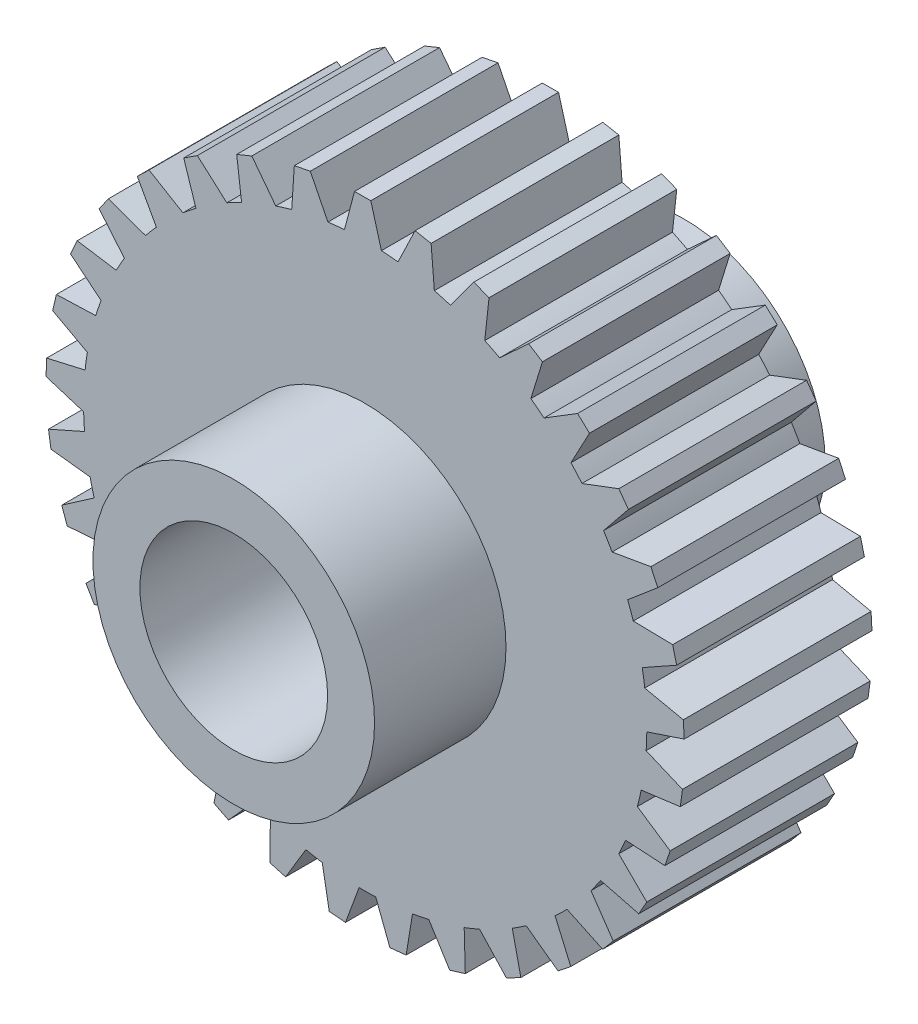
SolidWorks part; units mm, degrees
ref_plane "Front Plane" through (0, 0, 0) normal (0, 0, 1) x (1, 0, 0)
ref_plane "Top Plane" through (0, 0, 0) normal (0, 1, 0) x (1, 0, 0)
ref_plane "Right Plane" through (0, 0, 0) normal (1, 0, 0) x (0, 0, -1)
sketch "Sketch1" plane through (0, 0, 0) normal (0, 0, 1) x (1, 0, 0)
  line L0 (-1.1026, 14.9594) -> (-0.569, 16.9905)
  line L1 (-0.569, 16.9905) -> (0.2995, 16.9974)
  line L2 (0.2995, 16.9974) -> (0.8653, 14.975)
  line L3 (3.5108, 16.6335) -> (3.6837, 14.5406)
  line L4 (1.7484, 14.8978) -> (2.6568, 16.7911)
  line L5 (2.6568, 16.7911) -> (3.5108, 16.6335)
  line L6 (6.5953, 15.6685) -> (6.369, 13.5807)
  line L7 (4.5362, 14.2977) -> (5.7865, 15.9849)
  line L8 (5.7865, 15.9849) -> (6.5953, 15.6685)
  line L9 (9.4414, 14.1372) -> (8.824, 12.13)
  line L10 (7.1601, 13.1808) -> (8.7071, 14.6009)
  line L11 (8.7071, 14.6009) -> (9.4414, 14.1372)
  line L12 (11.9463, 12.0949) -> (10.9602, 10.2408)
  line L13 (9.5252, 11.5875) -> (11.313, 12.6892)
  line L14 (11.313, 12.6892) -> (11.9463, 12.0949)
  line L15 (14.0194, 9.6155) -> (12.7002, 7.9815)
  line L16 (11.546, 9.5755) -> (13.51, 10.3189)
  line L17 (13.51, 10.3189) -> (14.0194, 9.6155)
  line L18 (15.5857, 6.7886) -> (13.9812, 5.4338)
  line L19 (13.1495, 7.2174) -> (15.2187, 7.5757)
  line L20 (15.2187, 7.5757) -> (15.5857, 6.7886)
  line L21 (16.5888, 3.7163) -> (14.7569, 2.6896)
  line L22 (14.2778, 4.5984) -> (16.3774, 4.5586)
  line L23 (16.3774, 4.5586) -> (16.5888, 3.7163)
  line L24 (16.9924, 0.5096) -> (14.9992, -0.1518)
  line L25 (14.89, 1.8132) -> (16.9442, 1.3768)
  line L26 (16.9442, 1.3768) -> (16.9924, 0.5096)
  line L27 (16.7817, -2.7154) -> (14.6995, -2.9876)
  line L28 (14.9641, -1.0375) -> (16.8985, -1.8548)
  line L29 (16.8985, -1.8548) -> (16.7817, -2.7154)
  line L30 (15.9646, -5.8423) -> (13.8684, -5.7155)
  line L31 (14.4973, -3.8508) -> (16.2421, -5.0194)
  line L32 (16.2421, -5.0194) -> (15.9646, -5.8423)
  line L33 (14.5704, -8.758) -> (12.5361, -8.2369)
  line L34 (13.5066, -6.5248) -> (14.9987, -8.0025)
  line L35 (14.9987, -8.0025) -> (14.5704, -8.758)
  line L36 (12.6496, -11.3572) -> (10.7507, -10.4605)
  line L37 (12.0276, -8.963) -> (13.2131, -10.6964)
  line L38 (13.2131, -10.6964) -> (12.6496, -11.3572)
  line L39 (10.2717, -13.5459) -> (8.5768, -12.306)
  line L40 (10.114, -11.0773) -> (10.9501, -13.0037)
  line L41 (10.9501, -13.0037) -> (10.2717, -13.5459)
  line L42 (7.5225, -15.2451) -> (6.0929, -13.7068)
  line L43 (7.8349, -12.7912) -> (8.2912, -14.841)
  line L44 (8.2912, -14.841) -> (7.5225, -15.2451)
  line L45 (4.5014, -16.3932) -> (3.3887, -14.6122)
  line L46 (5.2725, -14.0428) -> (5.3327, -16.1419)
  line L47 (5.3327, -16.1419) -> (4.5014, -16.3932)
  line L48 (1.3176, -16.9489) -> (0.5621, -14.9895)
  line L49 (2.5196, -14.7869) -> (2.1814, -16.8595)
  line L50 (2.1814, -16.8595) -> (1.3176, -16.9489)
  line L51 (-1.9138, -16.8919) -> (-2.2848, -14.825)
  line L52 (-0.3243, -14.9965) -> (-1.0487, -16.9676)
  line L53 (-1.0487, -16.9676) -> (-1.9138, -16.8919)
  line L54 (-5.076, -16.2245) -> (-5.0492, -14.1247)
  line L55 (-3.1566, -14.6641) -> (-4.2408, -16.4625)
  line L56 (-4.2408, -16.4625) -> (-5.076, -16.2245)
  line L57 (-8.0548, -14.9706) -> (-7.631, -12.9138)
  line L58 (-5.8747, -13.8017) -> (-7.2798, -15.3625)
  line L59 (-7.2798, -15.3625) -> (-8.0548, -14.9706)
  line L60 (-10.7425, -13.1757) -> (-9.9371, -11.2363)
  line L61 (-8.3806, -12.4405) -> (-10.0556, -13.7071)
  line L62 (-10.0556, -13.7071) -> (-10.7425, -13.1757)
  line L63 (-13.0419, -10.9046) -> (-11.884, -9.1526)
  line L64 (-10.5835, -10.6297) -> (-12.468, -11.5564)
  line L65 (-12.468, -11.5564) -> (-13.0419, -10.9046)
  line L66 (-14.8699, -8.2393) -> (-13.4014, -6.7382)
  line L67 (-12.4039, -8.4346) -> (-14.4297, -8.988)
  line L68 (-14.4297, -8.988) -> (-14.8699, -8.2393)
  line L69 (-16.1605, -5.2763) -> (-14.4344, -4.0802)
  line L70 (-13.776, -5.9347) -> (-15.8699, -6.0947)
  line L71 (-15.8699, -6.0947) -> (-16.1605, -5.2763)
  line L72 (-16.867, -2.1226) -> (-14.9457, -1.2747)
  line L73 (-14.6502, -3.2204) -> (-16.7366, -2.9812)
  line L74 (-16.7366, -2.9812) -> (-16.867, -2.1226)
  line L75 (-16.9639, 1.1079) -> (-14.9169, 1.5768)
  line L76 (-14.9949, -0.3896) -> (-16.9983, 0.2401)
  line L77 (-16.9983, 0.2401) -> (-16.9639, 1.1079)
  line L78 (-16.4476, 4.2983) -> (-14.3489, 4.3714)
  line L79 (-14.7977, 2.4553) -> (-16.6457, 3.4527)
  line L80 (-16.6457, 3.4527) -> (-16.4476, 4.2983)
  line L81 (-15.3369, 7.3334) -> (-13.2623, 7.0079)
  line L82 (-14.0656, 5.2114) -> (-15.6914, 6.5405)
  line L83 (-15.6914, 6.5405) -> (-15.3369, 7.3334)
  line L84 (-13.6719, 10.1034) -> (-11.6964, 9.3912)
  line L85 (-12.8252, 7.7791) -> (-14.1701, 9.392)
  line L86 (-14.1701, 9.392) -> (-13.6719, 10.1034)
  line L87 (-11.5128, 12.5082) -> (-9.7077, 11.435)
  line L88 (-11.1212, 10.0657) -> (-12.1366, 11.904)
  line L89 (-12.1366, 11.904) -> (-11.5128, 12.5082)
  line L90 (-8.9375, 14.461) -> (-7.3682, 13.0656)
  line L91 (-9.0153, 11.9885) -> (-9.6644, 13.9857)
  line L92 (-9.6644, 13.9857) -> (-8.9375, 14.461)
  line L93 (-6.0393, 15.8911) -> (-4.7624, 14.2239)
  line L94 (-6.5835, 13.478) -> (-6.8429, 15.5619)
  line L95 (-6.8429, 15.5619) -> (-6.0393, 15.8911)
  line L96 (-2.9227, 16.7469) -> (-1.9844, 14.8682)
  line L97 (-3.9138, 14.4804) -> (-3.7742, 16.5758)
  line L98 (-3.7742, 16.5758) -> (-2.9227, 16.7469)
  arc A0 (1.7484, 14.8978) -> (0.8653, 14.975) centre (0, 0) ccw
  arc A1 (0.2995, 16.9974) -> (-0.569, 16.9905) centre (0, 0) ccw
  arc A2 (4.5362, 14.2977) -> (3.6837, 14.5406) centre (0, 0) ccw
  circle A3 centre (0, 0) radius 17 construction
  circle A4 centre (0, 0) radius 15 construction
  arc A5 (7.1601, 13.1808) -> (6.369, 13.5807) centre (0, 0) ccw
  arc A6 (9.5252, 11.5875) -> (8.824, 12.13) centre (0, 0) ccw
  arc A7 (11.546, 9.5755) -> (10.9602, 10.2408) centre (0, 0) ccw
  arc A8 (13.1495, 7.2174) -> (12.7002, 7.9815) centre (0, 0) ccw
  arc A9 (14.2778, 4.5984) -> (13.9812, 5.4338) centre (0, 0) ccw
  arc A10 (14.89, 1.8132) -> (14.7569, 2.6896) centre (0, 0) ccw
  arc A11 (14.9641, -1.0375) -> (14.9992, -0.1518) centre (0, 0) ccw
  arc A12 (14.4973, -3.8508) -> (14.6995, -2.9876) centre (0, 0) ccw
  arc A13 (13.5066, -6.5248) -> (13.8684, -5.7155) centre (0, 0) ccw
  arc A14 (12.0276, -8.963) -> (12.5361, -8.2369) centre (0, 0) ccw
  arc A15 (10.114, -11.0773) -> (10.7507, -10.4605) centre (0, 0) ccw
  arc A16 (7.8349, -12.7912) -> (8.5768, -12.306) centre (0, 0) ccw
  arc A17 (5.2725, -14.0428) -> (6.0929, -13.7068) centre (0, 0) ccw
  arc A18 (2.5196, -14.7869) -> (3.3887, -14.6122) centre (0, 0) ccw
  arc A19 (-0.3243, -14.9965) -> (0.5621, -14.9895) centre (0, 0) ccw
  arc A20 (-3.1566, -14.6641) -> (-2.2848, -14.825) centre (0, 0) ccw
  arc A21 (-5.8747, -13.8017) -> (-5.0492, -14.1247) centre (0, 0) ccw
  arc A22 (-8.3806, -12.4405) -> (-7.631, -12.9138) centre (0, 0) ccw
  arc A23 (-10.5835, -10.6297) -> (-9.9371, -11.2363) centre (0, 0) ccw
  arc A24 (-12.4039, -8.4346) -> (-11.884, -9.1526) centre (0, 0) ccw
  arc A25 (-13.776, -5.9347) -> (-13.4014, -6.7382) centre (0, 0) ccw
  arc A26 (-14.6502, -3.2204) -> (-14.4344, -4.0802) centre (0, 0) ccw
  arc A27 (-14.9949, -0.3896) -> (-14.9457, -1.2747) centre (0, 0) ccw
  arc A28 (-14.7977, 2.4553) -> (-14.9169, 1.5768) centre (0, 0) ccw
  arc A29 (-1.1026, 14.9594) -> (-1.9844, 14.8682) centre (0, 0) ccw
  arc A30 (-3.9138, 14.4804) -> (-4.7624, 14.2239) centre (0, 0) ccw
  arc A31 (-6.5835, 13.478) -> (-7.3682, 13.0656) centre (0, 0) ccw
  arc A32 (-9.0153, 11.9885) -> (-9.7077, 11.435) centre (0, 0) ccw
  arc A33 (-11.1212, 10.0657) -> (-11.6964, 9.3912) centre (0, 0) ccw
  arc A34 (-12.8252, 7.7791) -> (-13.2623, 7.0079) centre (0, 0) ccw
  arc A35 (-14.0656, 5.2114) -> (-14.3489, 4.3714) centre (0, 0) ccw
  point P7 (17, 0)
  point P11 (14.3446, 4.3856)
  point P140 (0, 0)
  dimension "D1" = 30
  dimension "D3" = 2.1
  dimension "D2" = 2
  dimension "D4" = 33
extrude "Boss-Extrude1" add sketch "Sketch1" along normal mid plane 10 contours L82 A35 L78 L80 L79 A28 L75 L77 L76 A27 L72 L74 L73 A26 L69 L71 L70 A25 L66 L68 L67 A24 L63 L65 L64 A23 L60 L62 L61 A22 L57 L59 L58 A21 L54 L56 L55 A20 L51 L53 L52 A19 L48 L50 L49 A18 L45 L47 L46 A17 L42 region at (0, 0, 0)
sketch "Sketch2" plane through (0, 0, 5) normal (0, 0, 1) x (1, 0, 0)
  circle A0 centre (0, 0) radius 7.5
  dimension "D1" = 15
extrude "Boss-Extrude2" add sketch "Sketch2" along normal blind 7
mirror "Mirror1" about plane through (0, 0, 0) normal (0, 0, 1) of "Boss-Extrude2"
sketch "Sketch3" plane through (0, 0, 12) normal (0, 0, 1) x (1, 0, 0)
  circle A0 centre (0, 0) radius 5
  dimension "D1" = 10
extrude "Cut-Extrude1" cut sketch "Sketch3" against normal through all both and the other way through all
